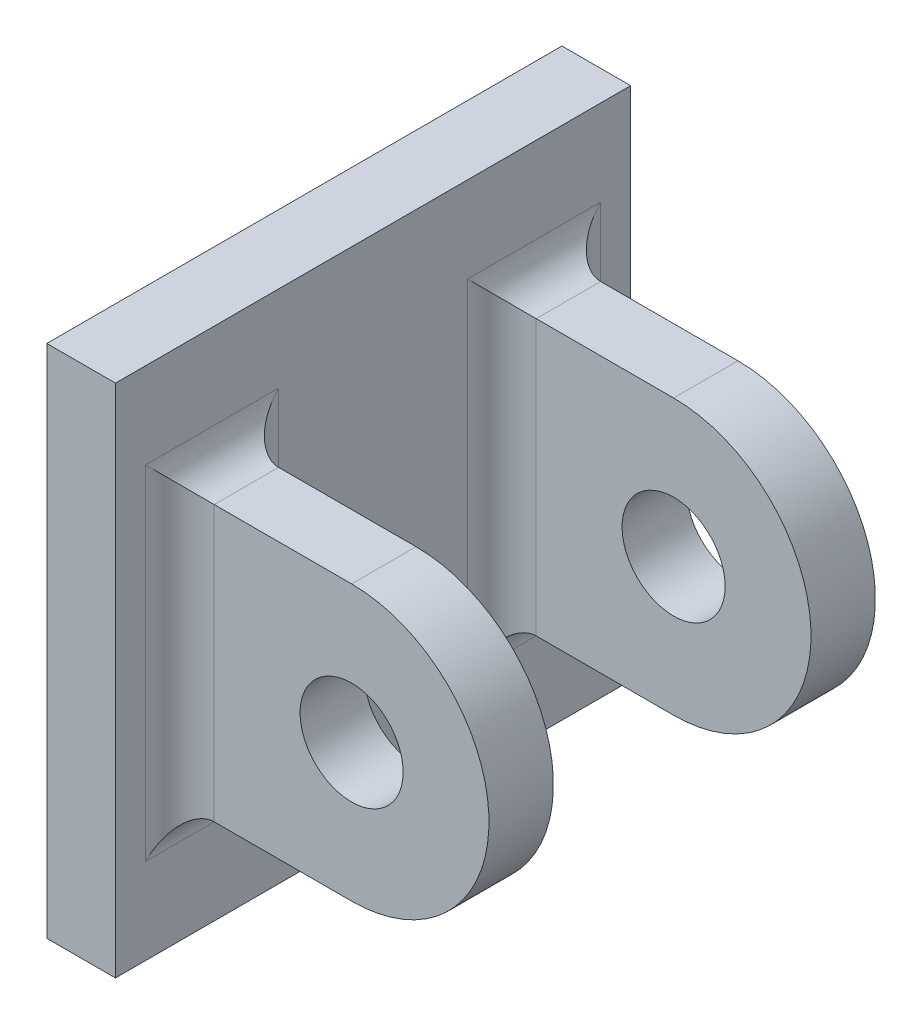
SolidWorks part; units mm, degrees
material "Inconel 718"
ref_plane "Front Plane" through (0, 0, 0) normal (0, 0, 1) x (1, 0, 0)
ref_plane "Top Plane" through (0, 0, 0) normal (0, 1, 0) x (1, 0, 0)
ref_plane "Right Plane" through (0, 0, 0) normal (1, 0, 0) x (0, 0, -1)
sketch "Sketch2" plane through (0, 0, 0) normal (1, 0, 0) x (0, 0, -1)
  line L1 (0, 0) -> (19.05, 0)
  line L2 (0, 0) -> (0, 19.05)
  line L3 (0, 19.05) -> (19.05, 19.05)
  line L4 (19.05, 0) -> (19.05, 19.05)
  dimension "D1" = 19.05
  dimension "D2" = 19.05
extrude "Boss-Extrude2" add sketch "Sketch2" along normal blind 2.54
sketch "Sketch3" plane through (2.54, 0, 0) normal (1, 0, 0) x (0, 0, -1)
  line L0 (0, 19.05) -> (0, 0) construction
  line L1 (2.3813, 14.605) -> (4.7625, 14.605)
  line L2 (2.3813, 14.605) -> (2.3813, 4.445)
  line L3 (2.3813, 4.445) -> (4.7625, 4.445)
  line L4 (4.7625, 14.605) -> (4.7625, 4.445)
  line L5 (14.2875, 14.605) -> (16.6688, 14.605)
  line L6 (14.2875, 14.605) -> (14.2875, 4.445)
  line L7 (14.2875, 4.445) -> (16.6688, 4.445)
  line L8 (16.6688, 14.605) -> (16.6688, 4.445)
  line L9 (19.05, 0) -> (19.05, 19.05) construction
  line L10 (0, 0) -> (19.05, 0) construction
  dimension "D1" = 4.7625
  dimension "D2" = 4.7625
  dimension "D3" = 10.16
  dimension "D4" = 10.16
  dimension "D5" = 2.3813
  dimension "D6" = 2.3813
  dimension "D7" = 4.445
  dimension "D8" = 4.445
extrude "Boss-Extrude3" add sketch "Sketch3" along normal blind 11.43
sketch "Sketch4" plane through (0, 0, -2.3813) normal (0, 0, 1) x (1, 0, 0)
  line L0 (8.89, 14.605) -> (13.97, 14.605)
  line L1 (13.97, 14.605) -> (13.97, 4.445)
  line L2 (13.97, 4.445) -> (8.89, 4.445)
  arc A0 (8.89, 4.445) -> (8.89, 14.605) centre (8.89, 9.525) ccw
  circle A1 centre (8.89, 9.525) radius 1.905
  line M5 (2.54, 4.445) -> (13.97, 4.445)
  line M6 (13.97, 4.445) -> (13.97, 14.605)
  line M7 (13.97, 14.605) -> (2.54, 14.605)
  dimension "D1" = 3.81
extrude "Cut-Extrude1" cut sketch "Sketch4" against normal through all contours A0 L1 M7 | A0 M5 M6 region at (12.8353, 5.5797, -2.3813) region at (12.8353, 13.4703, -2.3813)
extrude "Cut-Extrude2" cut sketch "Sketch4<4>" against normal through all contours A1 region at (8.89, 9.525, -2.3813)
sketch "Sketch4<4>" plane through (0, 0, -2.3813) normal (0, 0, 1) x (1, 0, 0) same geometry as "Sketch4"
fillet "Fillet3" radius 1.27 8 edges at (2.54, 9.525, -14.2875) (2.54, 14.605, -15.4781) (2.54, 4.445, -15.4781) (2.54, 9.525, -16.6688) (2.54, 9.525, -4.7625) (2.54, 4.445, -3.5719) (2.54, 9.525, -2.3813) (2.54, 14.605, -3.5719)
